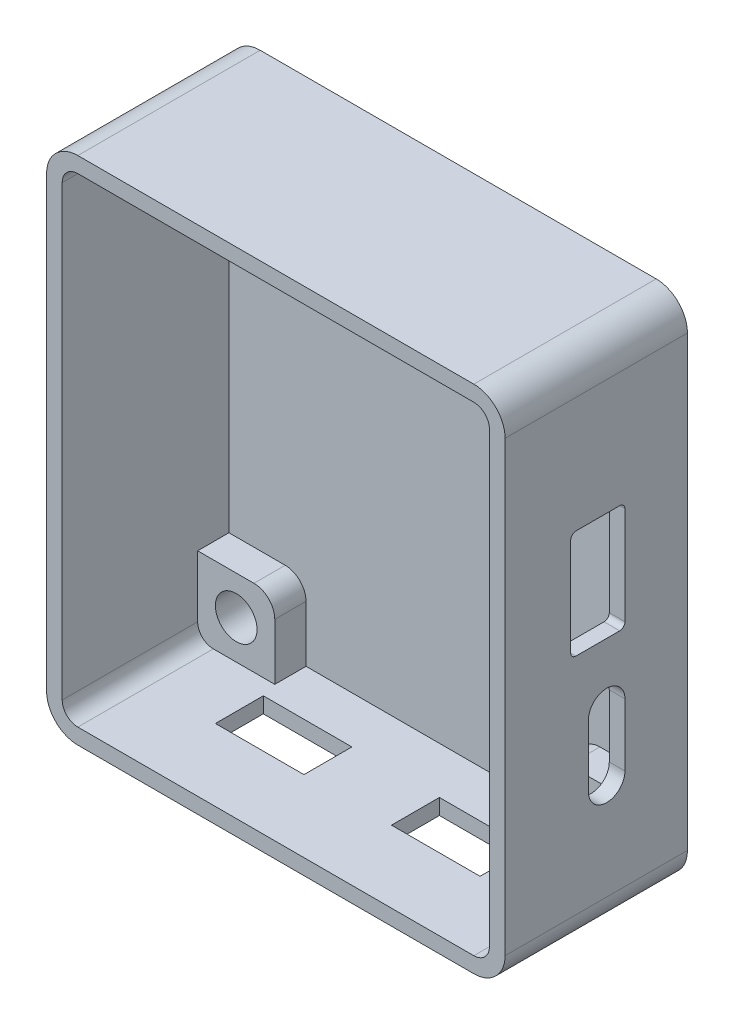
SolidWorks part; units mm, degrees
ref_plane "前视基准面" through (0, 0, 0) normal (0, 0, 1) x (1, 0, 0)
ref_plane "上视基准面" through (0, 0, 0) normal (0, 1, 0) x (1, 0, 0)
ref_plane "右视基准面" through (0, 0, 0) normal (1, 0, 0) x (0, 0, -1)
other "Configuration Table"
sketch "草图1" plane through (0, 0, 0) normal (0, 0, 1) x (1, 0, 0)
  line L1 (-19, -24.5) -> (19, -24.5)
  line L2 (-22, -21.5) -> (-22, 21.5)
  line L3 (-19, 24.5) -> (19, 24.5)
  line L4 (22, -21.5) -> (22, 21.5)
  line L5 (-22, -24.5) -> (22, 24.5) construction
  line L6 (-22, 24.5) -> (22, -24.5) construction
  arc A0 (19, -24.5) -> (22, -21.5) centre (19, -21.5) ccw
  arc A1 (-19, -24.5) -> (-22, -21.5) centre (-19, -21.5) cw
  arc A2 (19, 24.5) -> (22, 21.5) centre (19, 21.5) cw
  arc A3 (-22, 21.5) -> (-19, 24.5) centre (-19, 21.5) cw
  point P0 (0, 0)
  dimension "D3" = 3
  dimension "D1" = 49
  dimension "D2" = 44
extrude "凸台-拉伸1" add sketch "草图1" along normal blind 1.5
sketch "草图4" plane through (0, 0, 1.5) normal (0, 0, 1) x (1, 0, 0)
  line L0 (-19, -24.5) -> (19, -24.5) construction
  line L1 (-22, 21.5) -> (-22, -21.5) construction
  line L2 (22, -21.5) -> (22, 21.5) construction
  line L3 (19, 24.5) -> (-19, 24.5) construction
  line L4 (-19, -24.5) -> (19, -24.5)
  line L5 (-22, 21.5) -> (-22, -21.5)
  line L6 (22, -21.5) -> (22, 21.5)
  line L7 (19, 24.5) -> (-19, 24.5)
  line L8 (20.5, -21.5) -> (20.5, 21.5)
  line L9 (19, 23) -> (-19, 23)
  line L10 (-20.5, 21.5) -> (-20.5, -21.5)
  line L11 (-19, -23) -> (19, -23)
  arc A0 (-22, -21.5) -> (-19, -24.5) centre (-19, -21.5) ccw construction
  arc A1 (-19, 24.5) -> (-22, 21.5) centre (-19, 21.5) ccw construction
  arc A2 (19, -24.5) -> (22, -21.5) centre (19, -21.5) ccw construction
  arc A3 (22, 21.5) -> (19, 24.5) centre (19, 21.5) ccw construction
  arc A4 (-22, -21.5) -> (-19, -24.5) centre (-19, -21.5) ccw
  arc A5 (-19, 24.5) -> (-22, 21.5) centre (-19, 21.5) ccw
  arc A6 (19, -24.5) -> (22, -21.5) centre (19, -21.5) ccw
  arc A7 (22, 21.5) -> (19, 24.5) centre (19, 21.5) ccw
  arc A8 (20.5, 21.5) -> (19, 23) centre (19, 21.5) ccw
  arc A9 (-19, 23) -> (-20.5, 21.5) centre (-19, 21.5) ccw
  arc A10 (-20.5, -21.5) -> (-19, -23) centre (-19, -21.5) ccw
  arc A11 (19, -23) -> (20.5, -21.5) centre (19, -21.5) ccw
  dimension "D1" = 1.5
extrude "凸台-拉伸2" add sketch "草图4" along normal blind 16
sketch "草图6" plane through (0, 0, 1.5) normal (0, 0, 1) x (1, 0, 0)
  line L0 (-13.1, 23) -> (-13.1, 17.6)
  line L1 (19, 23) -> (-19, 23) construction
  line L2 (-15.1, 15.6) -> (-20.5, 15.6)
  line L3 (-20.5, 21.5) -> (-20.5, -21.5) construction
  line L4 (0, 23) -> (0, -32.9365) construction
  line L5 (-20.5, 0) -> (27.6187, 0) construction
  line L6 (15.1, 15.6) -> (20.5, 15.6)
  line L7 (13.1, 23) -> (13.1, 17.6)
  line L8 (-15.1, -15.6) -> (-20.5, -15.6)
  line L9 (-13.1, -23) -> (-13.1, -17.6)
  line L10 (13.1, -23) -> (13.1, -17.6)
  line L11 (15.1, -15.6) -> (20.5, -15.6)
  line L12 (-19, -23) -> (19, -23) construction
  line L13 (20.5, -21.5) -> (20.5, 21.5) construction
  line L14 (-19, -23) -> (19, -23)
  line L15 (-20.5, 21.5) -> (-20.5, -21.5)
  line L16 (19, 23) -> (-19, 23)
  line L17 (20.5, -21.5) -> (20.5, 21.5)
  circle A0 centre (-16.8, 19.3) radius 2
  arc A1 (-13.1, 17.6) -> (-15.1, 15.6) centre (-15.1, 17.6) cw
  circle A2 centre (16.8, 19.3) radius 2
  arc A3 (13.1, 17.6) -> (15.1, 15.6) centre (15.1, 17.6) ccw
  circle A4 centre (-16.8, -19.3) radius 2
  arc A5 (-13.1, -17.6) -> (-15.1, -15.6) centre (-15.1, -17.6) ccw
  arc A6 (13.1, -17.6) -> (15.1, -15.6) centre (15.1, -17.6) cw
  circle A7 centre (16.8, -19.3) radius 2
  arc A8 (19, -23) -> (20.5, -21.5) centre (19, -21.5) ccw construction
  arc A9 (-20.5, -21.5) -> (-19, -23) centre (-19, -21.5) ccw construction
  arc A10 (-19, 23) -> (-20.5, 21.5) centre (-19, 21.5) ccw construction
  arc A11 (20.5, 21.5) -> (19, 23) centre (19, 21.5) ccw construction
  arc A12 (19, -23) -> (20.5, -21.5) centre (19, -21.5) ccw
  arc A13 (-20.5, -21.5) -> (-19, -23) centre (-19, -21.5) ccw
  arc A14 (-19, 23) -> (-20.5, 21.5) centre (-19, 21.5) ccw
  arc A15 (20.5, 21.5) -> (19, 23) centre (19, 21.5) ccw
  point P11 (-13.1, 15.6)
  arc M7 (19, -23) -> (20.5, -21.5) centre (19, -21.5) ccw
  line M8 (20.5, -21.5) -> (20.5, 21.5)
  arc M9 (20.5, 21.5) -> (19, 23) centre (19, 21.5) ccw
  line M10 (19, 23) -> (-19, 23)
  arc M11 (-19, 23) -> (-20.5, 21.5) centre (-19, 21.5) ccw
  line M12 (-20.5, 21.5) -> (-20.5, -21.5)
  arc M13 (-20.5, -21.5) -> (-19, -23) centre (-19, -21.5) ccw
  line M14 (-19, -23) -> (19, -23)
  dimension "D5" = 4
  dimension "D6" = 2
  dimension "D1" = 3.7
  dimension "D2" = 3.7
  dimension "D3" = 7.4
  dimension "D4" = 7.4
extrude "凸台-拉伸4" add sketch "草图6" along normal blind 3 contours A1 L0 L2 A0 M10 M11 M12 | L7 A3 L6 A2 M8 M9 M10 | A6 L10 L11 A7 M14 M7 M8 | L9 A5 L8 A4 M12 M13 M14 region at (-13.2047, 20.3, 1.5) region at (16.05, 22.8953, 1.5) region at (-17.8, -15.7047, 1.5) region at (20.3953, -18.55, 1.5)
sketch "草图7" plane through (22, 0, 0) normal (1, 0, 0) x (0, 0, -1)
  line L0 (-17.5, 21.5) -> (0, 21.5) construction
  line L1 (-10.7, 10.4) -> (-6.5, 10.4)
  line L2 (-11.2, 9.9) -> (-11.2, 0.5)
  line L3 (-10.7, 0) -> (-6.5, 0)
  line L4 (-6, 9.9) -> (-6, 0.5)
  line L5 (-4.5, 15.6) -> (-4.5, 21.5) construction
  line L6 (-7.75, -5.9) -> (-7.75, -11.9) construction
  line L7 (-6, -5.9) -> (-6, -11.9)
  line L8 (-9.5, -5.9) -> (-9.5, -11.9)
  line L9 (-17.5, -21.5) -> (0, -21.5) construction
  line L10 (-4.5, -21.5) -> (-4.5, -15.6) construction
  arc A0 (-11.2, 0.5) -> (-10.7, 0) centre (-10.7, 0.5) ccw
  arc A1 (-6.5, 0) -> (-6, 0.5) centre (-6.5, 0.5) ccw
  arc A2 (-6.5, 10.4) -> (-6, 9.9) centre (-6.5, 9.9) cw
  arc A3 (-10.7, 10.4) -> (-11.2, 9.9) centre (-10.7, 9.9) ccw
  arc A4 (-6, -5.9) -> (-9.5, -5.9) centre (-7.75, -5.9) ccw
  arc A5 (-9.5, -11.9) -> (-6, -11.9) centre (-7.75, -11.9) ccw
  point P10 (-11.2, 0)
  point P15 (-6, 10.4)
  point P18 (-11.2, 10.4)
  point P21 (-7.75, -8.9)
  dimension "D5" = 0.5
  dimension "D1" = 11.1
  dimension "D2" = 1.5
  dimension "D3" = 5.2
  dimension "D4" = 10.4
  dimension "D6" = 9.6
  dimension "D7" = 6
  dimension "D8" = 3.5
  dimension "D9" = 1.5
extrude "切除-拉伸1" cut sketch "草图7" against normal up to surface (1.5 mm away) up to face at (20.5, 0, 7)
sketch "草图9" plane through (0, -24.5, 0) normal (0, -1, 0) x (1, 0, 0)
  line L0 (-19, 4.5) -> (-13.1, 4.5) construction
  line L1 (-12.7, 10.6) -> (-4.2, 10.6)
  line L2 (-12.7, 10.6) -> (-12.7, 6)
  line L3 (-12.7, 6) -> (-4.2, 6)
  line L4 (-4.2, 10.6) -> (-4.2, 6)
  line L5 (4.2, 10.6) -> (12.7, 10.6)
  line L6 (4.2, 10.6) -> (4.2, 6)
  line L7 (4.2, 6) -> (12.7, 6)
  line L8 (12.7, 10.6) -> (12.7, 6)
  line L9 (13.1, 4.5) -> (19, 4.5) construction
  line L10 (19, 17.5) -> (19, 0) construction
  line L11 (-19, 17.5) -> (-19, 0) construction
  dimension "D1" = 1.5
  dimension "D2" = 1.5
  dimension "D3" = 8.5
  dimension "D4" = 6.3
  dimension "D5" = 6.3
  dimension "D6" = 8.5
  dimension "D7" = 4.6
  dimension "D8" = 4.6
extrude "切除-拉伸2" cut sketch "草图9" against normal up to surface (1.5 mm away) up to face at (0, -23, 7)
